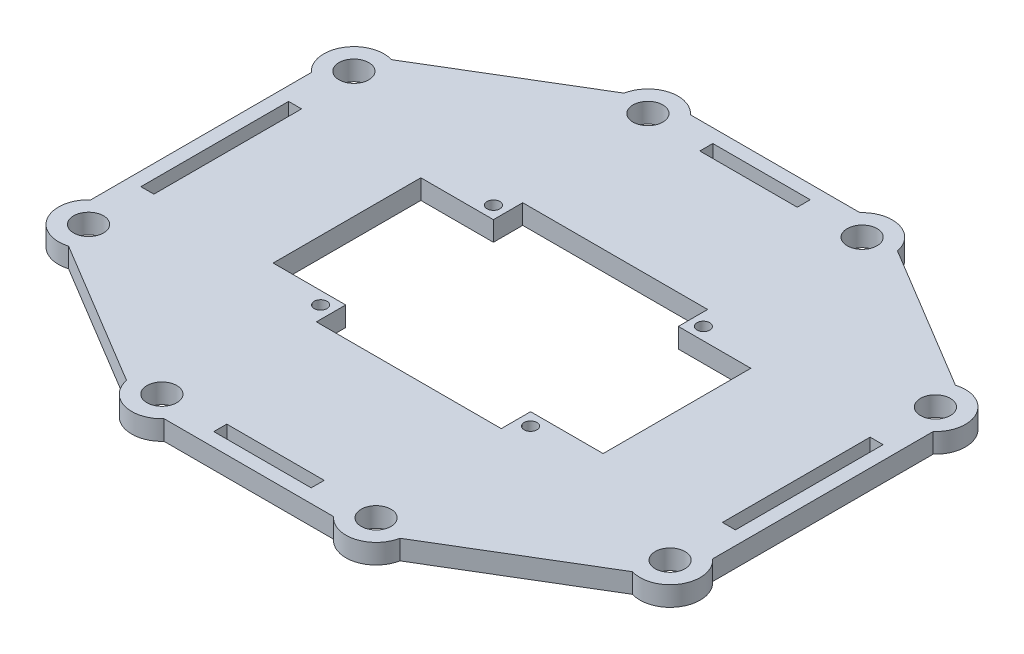
SolidWorks part; units mm, degrees
ref_plane "Front Plane" through (0, 0, 0) normal (0, 0, 1) x (1, 0, 0)
ref_plane "Top Plane" through (0, 0, 0) normal (0, 1, 0) x (1, 0, 0)
ref_plane "Right Plane" through (0, 0, 0) normal (1, 0, 0) x (0, 0, -1)
sketch "Sketch1" plane through (0, 0, 0) normal (0, 1, 0) x (1, 0, 0)
  line L0 (-75.3872, 32.1628) -> (-75.3872, -32.1628)
  line L1 (75.3872, 32.1628) -> (75.3872, -32.1627)
  line L2 (-25.9715, -63.8111) -> (25.9715, -63.8111)
  line L3 (-25.9715, 63.8112) -> (25.9715, 63.8111)
  line L4 (-73.0163, 36.3537) -> (-28.4901, 63.1126)
  line L5 (28.4901, 63.1126) -> (73.0163, 36.3537)
  line L6 (-73.0163, -36.3537) -> (-28.4901, -63.1126)
  line L7 (28.4901, -63.1126) -> (73.0163, -36.3537)
  line L8 (-73.0163, 36.3537) -> (-75.3872, 32.1628)
  line L9 (-75.3872, -32.1628) -> (-73.0163, -36.3537)
  line L10 (-28.4901, -63.1126) -> (-25.9715, -63.8111)
  line L11 (25.9715, -63.8111) -> (28.4901, -63.1126)
  line L12 (73.0163, -36.3537) -> (75.3872, -32.1627)
  line L13 (75.3872, 32.1628) -> (73.0163, 36.3537)
  line L14 (28.4901, 63.1126) -> (25.9715, 63.8111)
  line L15 (-25.9715, 63.8112) -> (-28.4901, 63.1126)
  line L16 (-40.005, 17.907) -> (-40.005, -17.907)
  line L17 (40.005, 17.907) -> (40.005, -17.907)
  line L18 (-22.4155, -25.019) -> (22.4155, -25.019)
  line L19 (-22.4155, 25.019) -> (22.4155, 25.019)
  line L20 (-40.005, 17.907) -> (-22.4155, 17.907)
  line L21 (40.005, 17.907) -> (22.4155, 17.907)
  line L22 (40.005, -17.907) -> (22.4155, -17.907)
  line L23 (-40.005, -17.907) -> (-22.4155, -17.907)
  line L24 (-22.4155, 25.019) -> (-22.4155, 17.907)
  line L25 (22.4155, 25.019) -> (22.4155, 17.907)
  line L26 (22.4155, -17.907) -> (22.4155, -25.019)
  line L27 (-22.4155, -17.907) -> (-22.4155, -25.019)
  line L29 (-68.9229, -17.907) -> (-72.0725, -17.907)
  line L30 (-68.9229, -17.907) -> (-68.9229, 17.907)
  line L31 (-68.9229, 17.907) -> (-72.0725, 17.907)
  line L32 (-72.0725, -17.907) -> (-72.0725, 17.907)
  line L33 (68.9229, 17.907) -> (72.0725, 17.907)
  line L34 (68.9229, 17.907) -> (68.9229, -17.907)
  line L35 (68.9229, -17.907) -> (72.0725, -17.907)
  line L36 (72.0725, 17.907) -> (72.0725, -17.907)
  line L37 (-11.811, -60.4964) -> (11.811, -60.4964)
  line L38 (-11.811, -60.4964) -> (-11.811, -57.3469)
  line L39 (-11.811, -57.3469) -> (11.811, -57.3469)
  line L40 (11.811, -60.4964) -> (11.811, -57.3469)
  line L41 (-11.811, 60.4964) -> (11.811, 60.4964)
  line L42 (-11.811, 60.4964) -> (-11.811, 57.3469)
  line L43 (-11.811, 57.3469) -> (11.811, 57.3469)
  line L44 (11.811, 60.4964) -> (11.811, 57.3469)
  circle A0 centre (25.9715, -58.9216) radius 7.3025
  circle A1 centre (25.9715, -58.9216) radius 3.6195
  circle A15 centre (-70.4977, 32.1628) radius 7.3025
  circle A16 centre (-70.4977, 32.1628) radius 3.6195
  circle A21 centre (-70.4977, -32.1628) radius 7.3025
  circle A22 centre (-70.4977, -32.1628) radius 3.6195
  circle A31 centre (70.4977, 32.1628) radius 7.3025
  circle A32 centre (70.4977, 32.1628) radius 3.6195
  circle A41 centre (70.4977, -32.1628) radius 7.3025
  circle A42 centre (70.4977, -32.1628) radius 3.6195
  circle A51 centre (25.9715, 58.9216) radius 7.3025
  circle A52 centre (25.9715, 58.9216) radius 3.6195
  circle A61 centre (-25.9715, 58.9216) radius 7.3025
  circle A62 centre (-25.9715, 58.9216) radius 3.6195
  circle A71 centre (-25.9715, -58.9216) radius 7.3025
  circle A72 centre (-25.9715, -58.9216) radius 3.6195
  circle A81 centre (-25.4572, 20.9487) radius 1.5558
  circle A82 centre (25.4572, 20.9487) radius 1.5557
  circle A83 centre (25.4572, -20.9487) radius 1.5557
  circle A84 centre (-25.4572, -20.9487) radius 1.5557
  point P2 (0, 0)
  point P3 (0, 0)
extrude "Boss-Extrude2" add sketch "Sketch1" along normal blind 4.7625 contours A71 L2 A0 L7 A41 L1 A31 L5 A51 L3 A61 L4 A15 L0 A21 L6 A84 A83 A82 A81 L40 L37 L38 L39 L27 L23 L16 L20 L24 L19 L25 L21 L17 L22 L26 L18 L29 L32 L31 L30 L33 L36 L35 | A15 | A21 | A71 | A0 | A41 | A31 | A51 | A61 region at (-66.7265, 0, -23.6859)
extrude "Cut-Extrude1" cut sketch "Sketch1<4>" against normal mid plane 9.525 contours A16 | A62 | A52 | A32 | A42 | A1 | A72 | A22
sketch "Sketch1<4>" plane through (0, 0, 0) normal (0, 1, 0) x (1, 0, 0) same geometry as "Sketch1"
